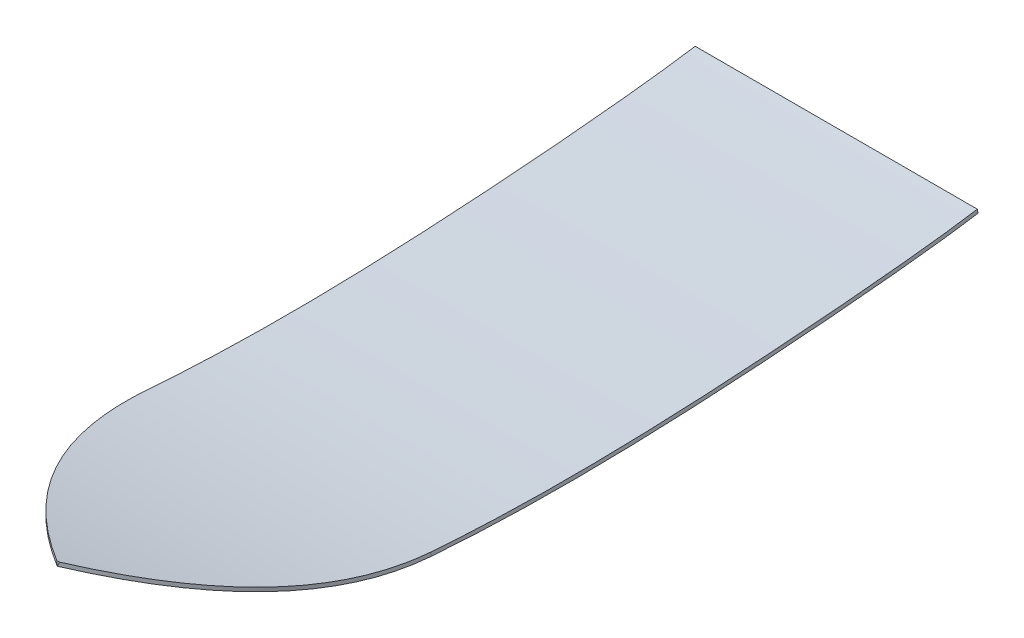
SolidWorks part; units mm, degrees
ref_plane "Front Plane" through (0, 0, 0) normal (0, 0, 1) x (1, 0, 0)
ref_plane "Top Plane" through (0, 0, 0) normal (0, 1, 0) x (1, 0, 0)
ref_plane "Right Plane" through (0, 0, 0) normal (1, 0, 0) x (0, 0, -1)
sketch "Sketch1" plane through (0, 0, 0) normal (1, 0, 0) x (0, 0, -1)
  line L24 (-2487.0915, 102.425) -> (-2493.1619, 78.1732)
  line L25 (2476.096, 16.0457) -> (2480.1147, -8.6292)
  spline S0 degree 3 poles (-2487.0915, 102.425) (-2403.1003, 81.4015) (-2258.2366, 47.4379) (-2029.4438, 0.0158) (-1849.8255, -32.3876) (-1684.9813, -58.5739) (-1558.666, -76.852) (-1418.8896, -94.8334) (-1276.7107, -110.8705) (-1131.6394, -124.9664) (-983.1162, -137.1076) (-831.6916, -147.1971) (-677.2231, -155.2224) (-519.7432, -161.1652) (-359.2322, -165.0291) (-195.7326, -166.8274) (-29.2846, -166.5914) (168.2562, -163.9945) (341.0559, -159.3559) (516.4607, -152.9035) (664.2159, -146.4214) (827.067, -137.8589) (932.9941, -131.5652) (993.8128, -127.7822) (1071.8943, -122.8444) (1210.4096, -113.4611) (1395.3562, -99.6437) (1577.9935, -84.7259) (1814.9806, -63.6462) (2147.9429, -29.9812) (2372.3285, -0.8546) (2476.096, 16.0457) knots 0.003558 0.003558 0.003558 0.003558 0.0625 0.105469 0.164062 0.1875 0.21875 0.25 0.28125 0.3125 0.34375 0.375 0.40625 0.4375 0.46875 0.5 0.53125 0.5625 0.609375 0.625 0.65625 0.6875 0.709961 0.710938 0.71875 0.75 0.78125 0.8125 0.84375 0.90625 1 1 1 1
  spline S1 degree 1 poles (-2493.1619, 78.1732) (2480.1147, -8.6292) knots 0 0 1 1 construction
  spline S2 degree 3 poles (-2493.1619, 78.1732) (-2482.0458, 75.3908) (-2459.7905, 69.8666) (-2415.3337, 59.0175) (-2359.7816, 45.8091) (-2293.1337, 30.5193) (-2204.2319, 10.8644) (-2092.9399, -12.3554) (-1958.8171, -38.1225) (-1823.7903, -61.8415) (-1642.1038, -90.7953) (-1457.231, -115.8142) (-1267.5304, -136.9625) (-1122.3264, -150.8904) (-973.7142, -162.8654) (-822.2487, -172.7928) (-667.7604, -180.6643) (-457.8092, -188.3952) (-187.8848, -192.8804) (91.7357, -190.6103) (320.916, -184.959) (495.4233, -178.8821) (672.425, -171.0509) (821.8809, -163.1465) (942.5307, -156.0495) (1063.9195, -148.4541) (1217.4664, -138.0199) (1401.8925, -124.2073) (1583.9685, -109.3056) (1761.1374, -93.5205) (1902.5464, -79.8024) (2010.6465, -68.5935) (2088.8869, -60.0956) (2163.9719, -51.5321) (2235.5822, -42.9287) (2292.0969, -35.7472) (2335.2543, -30.0073) (2366.5561, -25.708) (2396.7524, -21.4174) (2420.9629, -17.8515) (2439.7395, -15.006) (2453.5233, -12.8756) (2464.75, -11.1047) (2473.5891, -9.6882) (2477.9335, -8.9845) (2480.1147, -8.6292) knots 0.003558 0.003558 0.003558 0.003558 0.011343 0.019127 0.034697 0.050266 0.065836 0.096974 0.128113 0.159252 0.190391 0.252668 0.283807 0.314946 0.346085 0.377224 0.408363 0.439501 0.501779 0.564057 0.595195 0.626334 0.657473 0.688612 0.704181 0.719751 0.750889 0.782028 0.813167 0.844306 0.875445 0.891014 0.906584 0.922153 0.937722 0.953292 0.961076 0.968861 0.976646 0.984431 0.988323 0.992215 0.996108 0.998054 1 1 1 1
  dimension "D1" = 25
extrude "Boss-Extrude1" add sketch "Sketch1" along normal blind 1524 and the other way blind 1524
sketch "Sketch3" plane through (0, 0, 0) normal (0, 1, 0) x (1, 0, 0)
  line L0 (-900, 2508.1974) -> (900, 2508.1974)
  line L1 (-900, 2508.1974) -> (-900, -1009.3363)
  line L2 (900, 2508.1974) -> (900, -1009.3363)
  line L3 (0, 2955.5244) -> (0, -2061.9995) construction
  line L4 (-2934.2017, 5372.0277) -> (2797.2556, 5372.0277)
  line L5 (-2934.2017, 5372.0277) -> (-2934.2017, -2631.2782)
  line L6 (-2934.2017, -2631.2782) -> (2797.2556, -2631.2782)
  line L7 (2797.2556, 5372.0277) -> (2797.2556, -2631.2782)
  line L8 (-94.9374, 0) -> (0, 0) construction
  line L11 (-1524, 1954.9582) -> (1524, 1954.9582) construction
  spline S0 degree 2 poles (-900, -1009.3363) (-900, -1883.9749) (0, -2493.1619) knots 0 0 0 1 1 1
  spline S1 degree 2 poles (900, -1009.3363) (900, -1883.9749) (0, -2493.1619) knots 0 0 0 1 1 1
  dimension "D1" = 1800
extrude "Cut-Extrude1" cut sketch "Sketch3" against normal through all both and the other way through all
